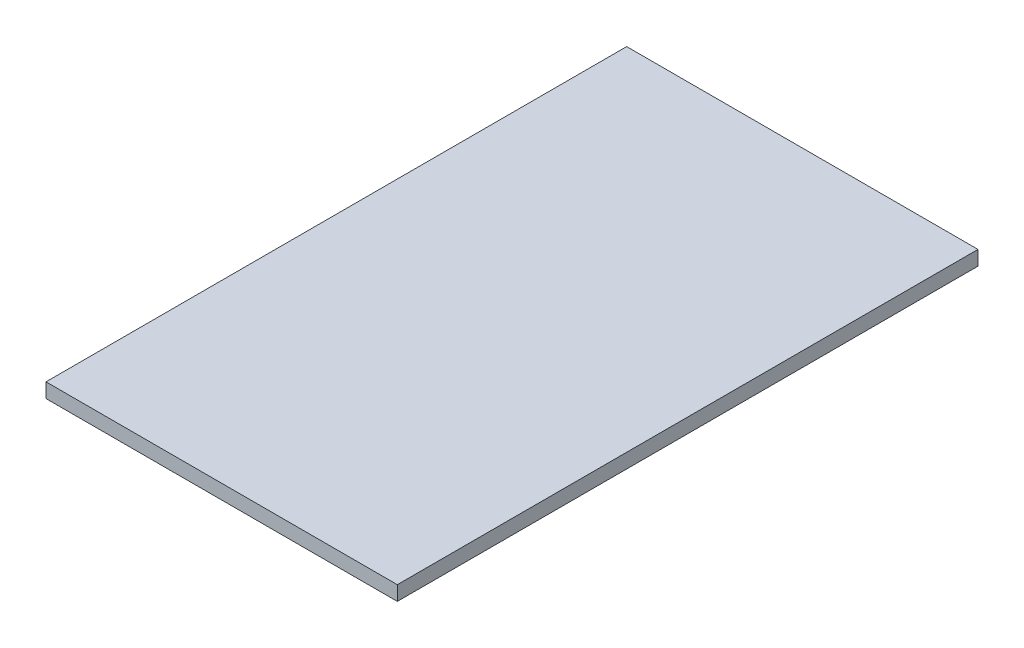
SolidWorks part; units mm, degrees
material "아크릴(내충격성)"
ref_plane "정면" through (0, 0, 0) normal (0, 0, 1) x (1, 0, 0)
ref_plane "윗면" through (0, 0, 0) normal (0, 1, 0) x (1, 0, 0)
ref_plane "우측면" through (0, 0, 0) normal (1, 0, 0) x (0, 0, -1)
sketch "스케치1" plane through (0, 0, 0) normal (0, 1, 0) x (1, 0, 0)
  line L1 (-60.5, 100) -> (60.5, 100)
  line L2 (-60.5, 100) -> (-60.5, -100)
  line L3 (-60.5, -100) -> (60.5, -100)
  line L4 (60.5, 100) -> (60.5, -100)
  line L5 (-60.5, 100) -> (60.5, -100) construction
  line L6 (-60.5, -100) -> (60.5, 100) construction
  point P0 (0, 0)
  dimension "D1" = 121
  dimension "D2" = 200
extrude "보스-돌출1" add sketch "스케치1" along normal blind 5
